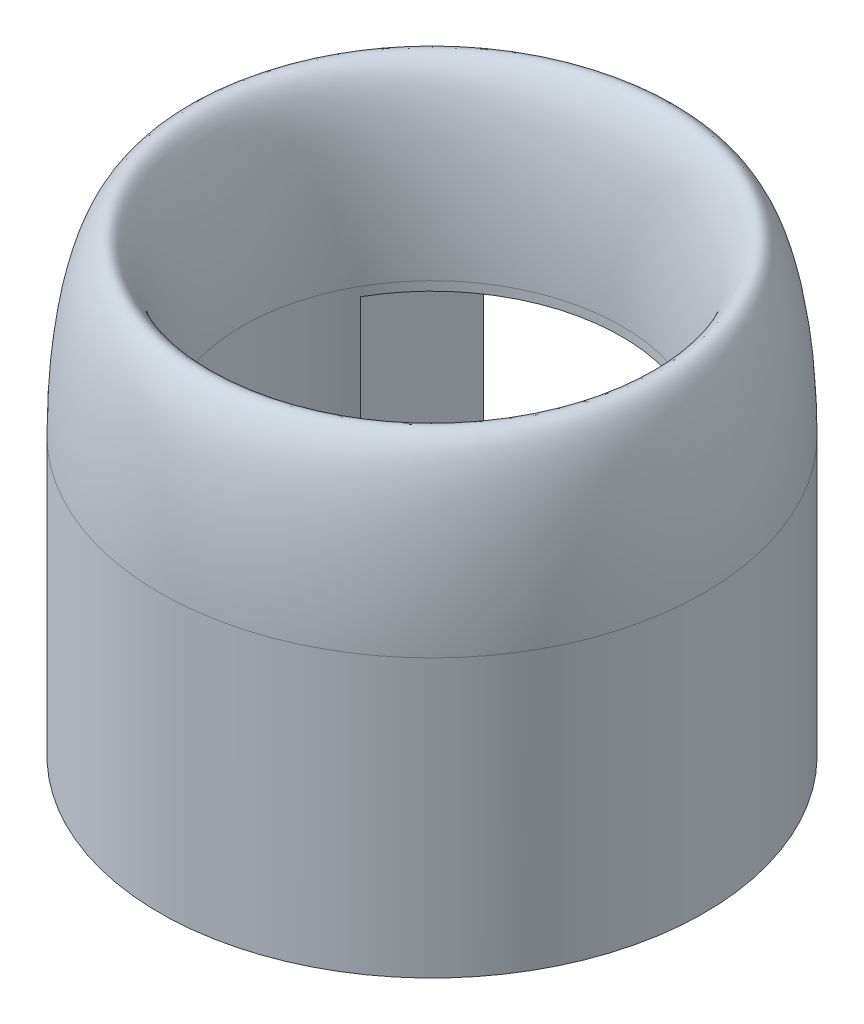
SolidWorks part; units mm, degrees
ref_plane "Front Plane" through (0, 0, 0) normal (0, 0, 1) x (1, 0, 0)
ref_plane "Top Plane" through (0, 0, 0) normal (0, 1, 0) x (1, 0, 0)
ref_plane "Right Plane" through (0, 0, 0) normal (1, 0, 0) x (0, 0, -1)
sketch "Sketch1" plane through (0, 0, 0) normal (0, 1, 0) x (1, 0, 0)
  line L1 (-29, -29) -> (29, -29) construction
  line L2 (-29, -29) -> (-29, 29) construction
  line L3 (-29, 29) -> (29, 29) construction
  line L4 (29, -29) -> (29, 29) construction
  line L5 (0, 29) -> (0, -29) construction
  line L6 (-29, 0) -> (29, 0) construction
  circle A0 centre (-19, 0) radius 1.8
  circle A1 centre (19, 0) radius 1.8
  circle A4 centre (0, 0) radius 5.5
  circle A5 centre (0, 0) radius 25
  point P0 (0, 0)
  dimension "D3" = 3.6
  dimension "D5" = 10
  dimension "D6" = 11
  dimension "D2" = 50
  dimension "D1" = 58
extrude "Boss-Extrude1" add sketch "Sketch1" along normal blind 7.5
sketch "Sketch2" plane through (0, 7.5, 0) normal (0, 1, 0) x (1, 0, 0)
  circle A4 centre (-19, 0) radius 4
  circle A5 centre (19, 0) radius 4
  dimension "D1" = 8
  dimension "D2" = 8
extrude "Cut-Extrude1" cut sketch "Sketch2" against normal blind 6
sketch "Sketch3" plane through (0, 0, 0) normal (0, -1, 0) x (1, 0, 0)
  circle A0 centre (0, 0) radius 33
  circle A1 centre (0, 0) radius 23
  circle A2 centre (-19, 0) radius 4 construction
  dimension "D1" = 10
extrude "Boss-Extrude2" add sketch "Sketch3" against normal blind 47 from surface starting at face at (-19, 7.5, 4)
extrude "Boss-Extrude3" add sketch "Sketch3<2>" against normal up to surface (7.5 mm away) up to face at (0, 7.5, 5.5)
sketch "Sketch3<2>" plane through (0, 0, 0) normal (0, -1, 0) x (1, 0, 0) same geometry as "Sketch3"
sketch "Sketch6" plane through (0, 0, 0) normal (0, 0, 1) x (1, 0, 0)
  line L0 (-33, 33.6) -> (-22.8047, 33.6) construction
  line L1 (-23, 54.5) -> (-23, 7.5) construction
  line L3 (-33, 54.5) -> (-33, 0) construction
  line L5 (-33, 33.6) -> (-33, 54.5)
  line L6 (-33, 54.5) -> (-23, 54.5)
  line L7 (-23, 54.5) -> (-23, 33.6)
  ellipse E0 centre (-28, 33.6) end of major axis (-28, 12.8) minor radius 5 (-23, 33.6) -> (-33, 33.6) ccw
  dimension "D1" = 0.1
  dimension "D2" = 20.9
revolve "Cut-Revolve7" cut sketch "Sketch6" angle 360 about axis through (0, 54.5, 0) along (0, -1, 0)
sketch "Sketch7" plane through (0, 7.5, 0) normal (0, 1, 0) x (1, 0, 0)
  line L1 (-20, 33) -> (20, 33)
  line L2 (-20, 33) -> (-20, 11.3578)
  line L3 (-20, 11.3578) -> (20, 11.3578)
  line L4 (20, 33) -> (20, 11.3578)
  line L5 (-20, 33) -> (20, 11.3578) construction
  line L6 (-20, 11.3578) -> (20, 33) construction
  circle A0 centre (0, 0) radius 33 construction
  arc A1 (23, 0) -> (-23, 0) centre (0, 0) ccw construction
  point P0 (0, 22.1789)
  point P5 (0, 0)
  point P7 (20, 28.7715)
  point P10 (0, 0)
  dimension "D1" = 40
extrude "Cut-Extrude3" cut sketch "Sketch7" along normal blind 25
